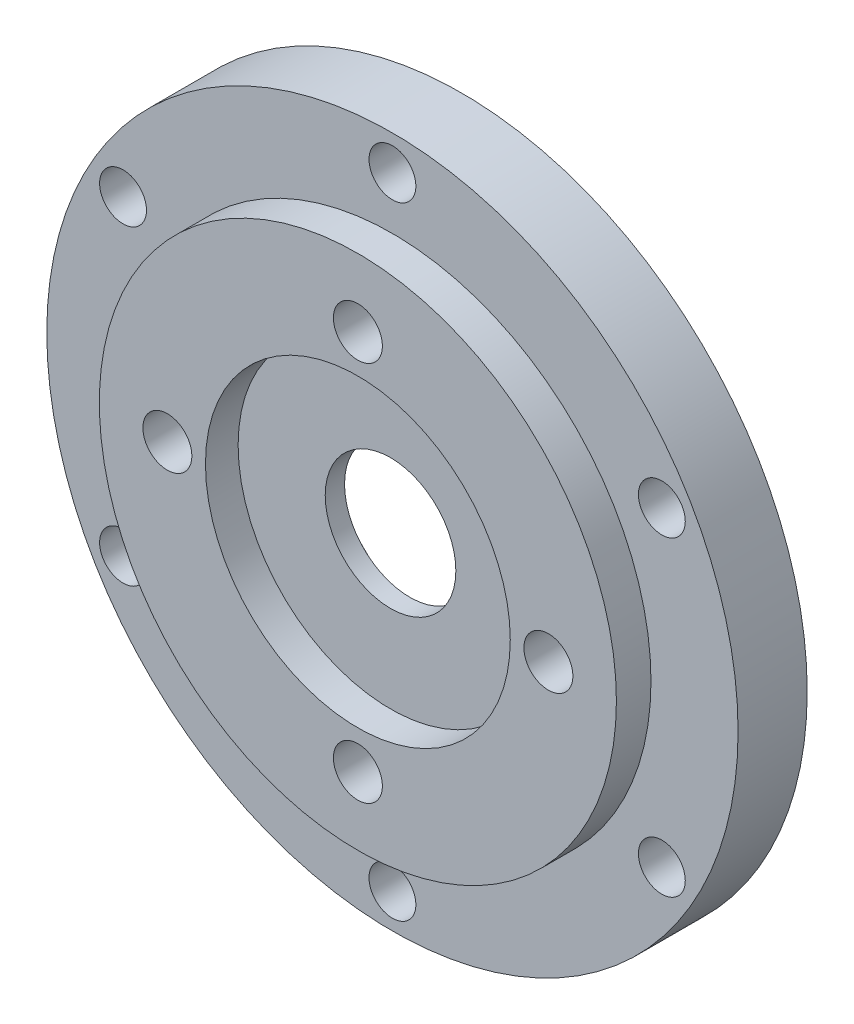
SolidWorks part; units mm, degrees
material "6061-T6 (SS)"
ref_plane "Front Plane" through (0, 0, 0) normal (0, 0, 1) x (1, 0, 0)
ref_plane "Top Plane" through (0, 0, 0) normal (0, 1, 0) x (1, 0, 0)
ref_plane "Right Plane" through (0, 0, 0) normal (1, 0, 0) x (0, 0, -1)
sketch "Sketch1" plane through (0, 0, 0) normal (0, 0, 1) x (1, 0, 0)
  circle A0 centre (0, 0) radius 31.75
  dimension "D1" = 63.5
extrude "Boss-Extrude1" add sketch "Sketch1" along normal blind 9.525
sketch "Sketch2" plane through (0, 0, 9.525) normal (0, 0, 1) x (1, 0, 0)
  circle A0 centre (0, 0) radius 14
  dimension "D1" = 28
extrude "Cut-Extrude1" cut sketch "Sketch2" against normal blind 3
hole_wizard "#8 Clearance Hole1" positions "Sketch4" profile "Sketch3" hole size "#8" standard "Ansi Inch" end condition through all
sketch "Sketch4" plane through (0, 0, 9.525) normal (0, 0, 1) x (1, 0, 0)
  point P0 (0, 28.575)
  point P9 (24.7467, 14.2875)
  point P10 (24.7467, -14.2875)
  point P11 (0, -28.575)
  point P12 (-24.7467, -14.2875)
  point P13 (-24.7467, 14.2875)
  dimension "D1" = 28.575
sketch "Sketch3" plane through (0, 28.575, 9.525) normal (1, 0, 0) x (0, -1, 0)
  line L0 (0, 0) -> (0, 9.525)
  line L1 (0, 9.525) -> (2.1526, 9.525)
  line L2 (2.1526, 9.525) -> (2.1526, 0)
  line L5 (2.1526, 0) -> (0, 0)
  line L11 (0, -6.35) -> (0, 107.95) construction
  dimension "Thru Hole Dia." = 4.3053
  dimension "Thru Hole Depth" = 9.525
sketch "Sketch5" plane through (0, 0, 0) normal (0, 0, -1) x (-1, 0, 0)
  circle A0 centre (0, 0) radius 12.7
  dimension "D1" = 25.4
extrude "Cut-Extrude2" cut sketch "Sketch5" against normal blind 4.7498
sketch "Sketch6" plane through (0, 0, 4.7498) normal (0, 0, -1) x (-1, 0, 0)
  circle A0 centre (0, 0) radius 6
  dimension "D1" = 12
extrude "Cut-Extrude3" cut sketch "Sketch6" against normal through all
hole_wizard "CBORE for M4 SHCS1" positions "Sketch8" profile "Sketch7" counterbore size "M4" standard "Ansi Metric" end condition through all
sketch "Sketch8" plane through (0, 0, 0) normal (0, 0, -1) x (-1, 0, 0)
  point P0 (0, 17.5)
  point P9 (17.5, 0)
  point P10 (0, -17.5)
  point P11 (-17.5, 0)
  dimension "D1" = 17.5
sketch "Sketch7" plane through (0, 17.5, 0) normal (1, 0, 0) x (0, 1, 0)
  line L0 (0, 0) -> (0, 9.525)
  line L1 (0, 9.525) -> (2.25, 9.525)
  line L3 (2.25, 9.525) -> (2.25, 4)
  line L4 (2.25, 4) -> (4, 4)
  line L5 (4, 4) -> (4, 0)
  line L7 (4, 0) -> (0, 0)
  line L11 (0, -6.35) -> (0, 107.95) construction
  dimension "Thru Hole Dia." = 4.5
  dimension "Thru Hole Depth" = 9.525
  dimension "C'Bore Dia." = 8
  dimension "C'Bore Depth" = 4
sketch "Sketch9" plane through (0, 0, 9.525) normal (0, 0, 1) x (1, 0, 0)
  circle A0 centre (0, 0) radius 23.749
  dimension "D1" = 47.498
extrude "Cut-Extrude4" cut sketch "Sketch9" against normal blind 3.175 flip side to cut
